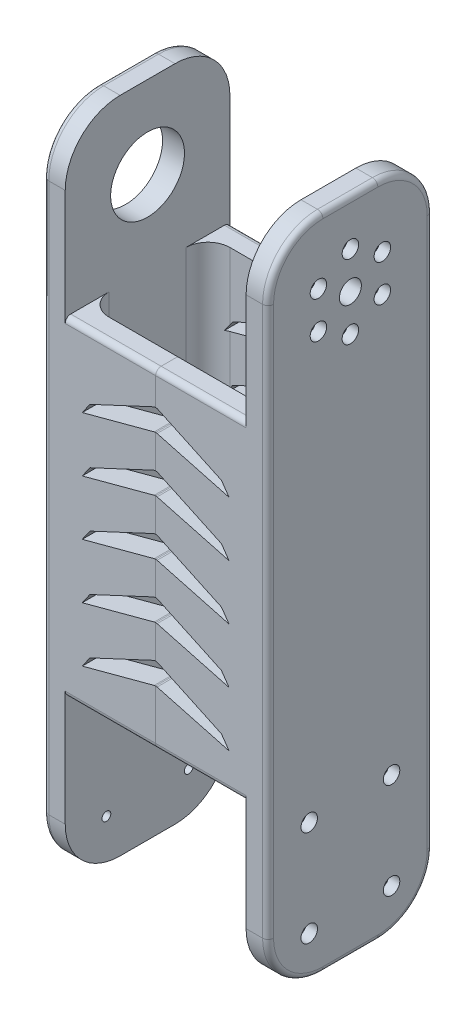
SolidWorks part; units mm, degrees
ref_plane "前视基准面" through (0, 0, 0) normal (0, 0, 1) x (1, 0, 0)
ref_plane "上视基准面" through (0, 0, 0) normal (0, 1, 0) x (1, 0, 0)
ref_plane "右视基准面" through (0, 0, 0) normal (1, 0, 0) x (0, 0, -1)
other "Configuration Table"
sketch "草图1" plane through (0, 0, 0) normal (1, 0, 0) x (0, 0, -1)
  line L1 (30, -120) -> (-30, -120)
  line L2 (30, -120) -> (30, 120)
  line L3 (30, 120) -> (-30, 120)
  line L4 (-30, -120) -> (-30, 120)
  line L5 (30, -120) -> (-30, 120) construction
  line L6 (30, 120) -> (-30, -120) construction
  point P0 (0, 0)
  dimension "D1" = 240
  dimension "D2" = 60
extrude "凸台-拉伸1" add sketch "草图1" along normal blind 8
sketch "草图2" plane through (8, 0, 0) normal (1, 0, 0) x (0, 0, -1)
  line L1 (30, 120) -> (-30, 120) construction
  circle A12 centre (0, 90) radius 13.45
  point P6 (0, 120)
  point P26 (0, 90)
  dimension "D11" = 26.9
  dimension "D2" = 30
extrude "切除-拉伸1" cut sketch "草图2" against normal through all
sketch "草图3" plane through (8, 0, 0) normal (1, 0, 0) x (0, 0, -1)
  line L0 (-30, 120) -> (-30, -120) construction
  line L1 (-22, -60) -> (-30, -60)
  line L2 (-22, -60) -> (-22, 60)
  line L3 (-22, 60) -> (-30, 60)
  line L4 (-30, -60) -> (-30, 60)
  line L5 (-22, -60) -> (-30, 60) construction
  line L6 (-22, 60) -> (-30, -60) construction
  line L7 (30, -60) -> (22, -60)
  line L8 (30, -60) -> (30, 60)
  line L9 (30, 60) -> (22, 60)
  line L10 (22, -60) -> (22, 60)
  line L11 (30, -60) -> (22, 60) construction
  line L12 (30, 60) -> (22, -60) construction
  line L13 (30, -120) -> (30, 120) construction
  line L14 (30, 120) -> (-30, 120) construction
  line L15 (-30, -120) -> (30, -120) construction
  point P0 (-26, 0)
  point P5 (26, 0)
  dimension "D1" = 60
  dimension "D2" = 60
  dimension "D3" = 60
  dimension "D4" = 60
  dimension "D5" = 8
  dimension "D6" = 8
extrude "凸台-拉伸2" add sketch "草图3" along normal blind 65.9
sketch "草图4" plane through (73.9, 0, 0) normal (1, 0, 0) x (0, 0, -1)
  line L0 (30, -120) -> (-30, 120) construction
  line L1 (30, -120) -> (-30, -120)
  line L2 (30, -120) -> (30, 120)
  line L3 (30, 120) -> (-30, 120)
  line L4 (-30, -120) -> (-30, 120)
  line L5 (30, -120) -> (-30, 120) construction
  line L6 (30, 120) -> (-30, -120) construction
  line L7 (30, 120) -> (-30, 120) construction
  point P0 (0, 0)
extrude "凸台-拉伸3" add sketch "草图4" along normal blind 8
fillet "圆角1" radius 20 8 edges at (4, -120, 30) (4, -120, -30) (4, 120, -30) (4, 120, 30) (77.9, 120, -30) (77.9, 120, 30) (77.9, -120, -30) (77.9, -120, 30)
sketch "草图9" plane through (73.9, 0, 0) normal (-1, 0, 0) x (0, 0, 1)
  circle A0 centre (0, 90) radius 19 construction
  circle A2 centre (0, 109) radius 1.6
  circle A3 centre (19, 90) radius 1.6
  circle A4 centre (0, 71) radius 1.6
  circle A5 centre (-19, 90) radius 1.6
  point P14 (0, 90)
  dimension "D1" = 38
  dimension "D2" = 3.2
sketch "草图10" plane through (81.9, 0, 0) normal (1, 0, 0) x (0, 0, -1)
  circle A0 centre (0, 90) radius 4
  circle A1 centre (0, 90) radius 13.5 construction
  circle A2 centre (0, 103.5) radius 1.6
  circle A3 centre (11.6913, 96.75) radius 1.6
  circle A4 centre (11.6913, 83.25) radius 1.6
  circle A5 centre (0, 76.5) radius 1.6
  circle A6 centre (-11.6913, 83.25) radius 1.6
  circle A7 centre (-11.6913, 96.75) radius 1.6
  point P18 (0, 90)
  dimension "D1" = 8
  dimension "D2" = 27
  dimension "D3" = 3.2
  dimension "D4" = 6
extrude "切除-拉伸2" cut sketch "草图10" against normal up to next
sketch "草图15" plane through (73.9, 0, 0) normal (-1, 0, 0) x (0, 0, 1)
  circle A0 centre (0, 90) radius 18
  dimension "D1" = 36
extrude "凸台-拉伸4" add sketch "草图15" along normal blind 9.8
sketch "草图11" plane through (81.9, 0, 0) normal (1, 0, 0) x (0, 0, -1)
  line L1 (15, -105) -> (-15, -105) construction
  line L2 (15, -105) -> (15, -70) construction
  line L3 (15, -70) -> (-15, -70) construction
  line L4 (-15, -105) -> (-15, -70) construction
  line L5 (15, -105) -> (-15, -70) construction
  line L6 (15, -70) -> (-15, -105) construction
  line L7 (-30, 100) -> (-30, -100) construction
  line L8 (30, -100) -> (30, 100) construction
  line L9 (0, -70) -> (0, -105) construction
  line L10 (-15, -87.5) -> (15, -87.5) construction
  line L11 (-22, -60) -> (-30, -60) construction
  circle A0 centre (-15, -70) radius 1.6
  circle A1 centre (15, -70) radius 1.6
  circle A2 centre (15, -105) radius 1.6
  circle A3 centre (-15, -105) radius 1.6
  point P0 (0, -87.5)
  dimension "D5" = 3.2
  dimension "D1" = 10
  dimension "D2" = 15
  dimension "D3" = 15
  dimension "D4" = 35
extrude "切除-拉伸3" cut sketch "草图11" against normal through all
sketch "草图12" plane through (81.9, 0, 0) normal (1, 0, 0) x (0, 0, -1)
  circle A0 centre (0, 103.45) radius 3
  circle A1 centre (0, 90) radius 13.45 construction
  circle A2 centre (11.648, 96.725) radius 3
  circle A3 centre (11.648, 83.275) radius 3
  circle A4 centre (0, 76.55) radius 3
  circle A5 centre (-11.648, 83.275) radius 3
  circle A6 centre (-11.648, 96.725) radius 3
  point P16 (0, 90)
  dimension "D1" = 6
  dimension "D2" = 6
extrude "切除-拉伸4" cut sketch "草图12" against normal blind 4
sketch "草图13" plane through (81.9, 0, 0) normal (1, 0, 0) x (0, 0, -1)
  line L2 (0, -70) -> (0, -105) construction
  line L3 (-15, -87.5) -> (15, -87.5) construction
  circle A0 centre (-15, -70) radius 3
  circle A1 centre (15, -70) radius 3
  circle A2 centre (15, -105) radius 3
  circle A3 centre (-15, -105) radius 3
  dimension "D1" = 6
extrude "切除-拉伸5" cut sketch "草图13" against normal blind 4
sketch "草图14" plane through (0, 0, 0) normal (-1, 0, 0) x (0, 0, 1)
  line L0 (0, -70) -> (0, -105) construction
  line L1 (-15, -87.5) -> (15, -87.5) construction
  circle A0 centre (-15, -70) radius 3
  circle A1 centre (15, -70) radius 3
  circle A2 centre (15, -105) radius 3
  circle A3 centre (-15, -105) radius 3
  dimension "D1" = 6
extrude "切除-拉伸6" cut sketch "草图14" against normal blind 4
extrude "切除-拉伸7" cut sketch "草图10<2>" against normal up to next
sketch "草图10<2>" plane through (81.9, 0, 0) normal (1, 0, 0) x (0, 0, -1) same geometry as "草图10"
ref_plane "基准面1" through (40.95, 0, 0) normal (1, 0, 0) x (0, 0, -1)
fillet "圆角2" radius 8 4 edges at (8, 0, -22) (73.9, 0, -22) (8, 0, 22) (73.9, 0, 22)
fillet "圆角3" radius 2 20 edges at (40.95, -60, 30) (40.95, -60, -30) (40.95, 60, 30) (40.95, 60, -30) (0, -114.1421, -24.1421) (0, -120, 0) (0, -114.1421, 24.1421) (0, 0, 30) (0, 114.1421, 24.1421) (0, 120, 0) (0, 114.1421, -24.1421) (81.9, -114.1421, -24.1421) (81.9, -120, 0) (81.9, -114.1421, 24.1421) (81.9, 0, 30) (81.9, 114.1421, 24.1421) (81.9, 120, 0) (81.9, 114.1421, -24.1421) (0, 0, -30) (81.9, 0, -30)
sketch "草图16" plane through (0, 0, -30) normal (0, 0, -1) x (-1, 0, 0)
  line L0 (-41.7952, -32.2261) -> (-64.9, -43)
  line L1 (-40.95, 30.8) -> (-40.95, -30.8) construction
  line L2 (-64.9, -43) -> (-67.7016, -47)
  line L3 (-67.7016, -47) -> (-41.4676, -39.9706)
  line L4 (-40.4324, -39.9706) -> (-14.1984, -47)
  line L5 (-14.1984, -47) -> (-17, -43)
  line L6 (-17, -43) -> (-40.1048, -32.2261)
  line L7 (-2, -100) -> (-2, 100) construction
  line L8 (-73.9, -58) -> (-8, -58) construction
  arc A0 (-41.4676, -39.9706) -> (-40.4324, -39.9706) centre (-40.95, -41.9025) cw
  arc A1 (-41.7952, -32.2261) -> (-40.1048, -32.2261) centre (-40.95, -34.0387) cw
  point P4 (-40.95, -14.2268)
  point P13 (0, 0)
  point P14 (-40.95, -14.2268)
  point P17 (-40.95, -39.8319)
  point P20 (-40.95, -31.8319)
  dimension "D8" = 2
  dimension "D1" = 65
  dimension "D2" = 65
  dimension "D3" = 15
  dimension "D4" = 11
  dimension "D5" = 4
  dimension "D6" = 150
  dimension "D7" = 8
extrude "切除-拉伸8" cut sketch "草图16" against normal through all
pattern_linear "阵列(线性)1" count 5 spacing 20 along (0, 1, 0) of "切除-拉伸8"
split "分割1" trim tools "基准面1" bodies to split 128 resulting bodies 125 126
